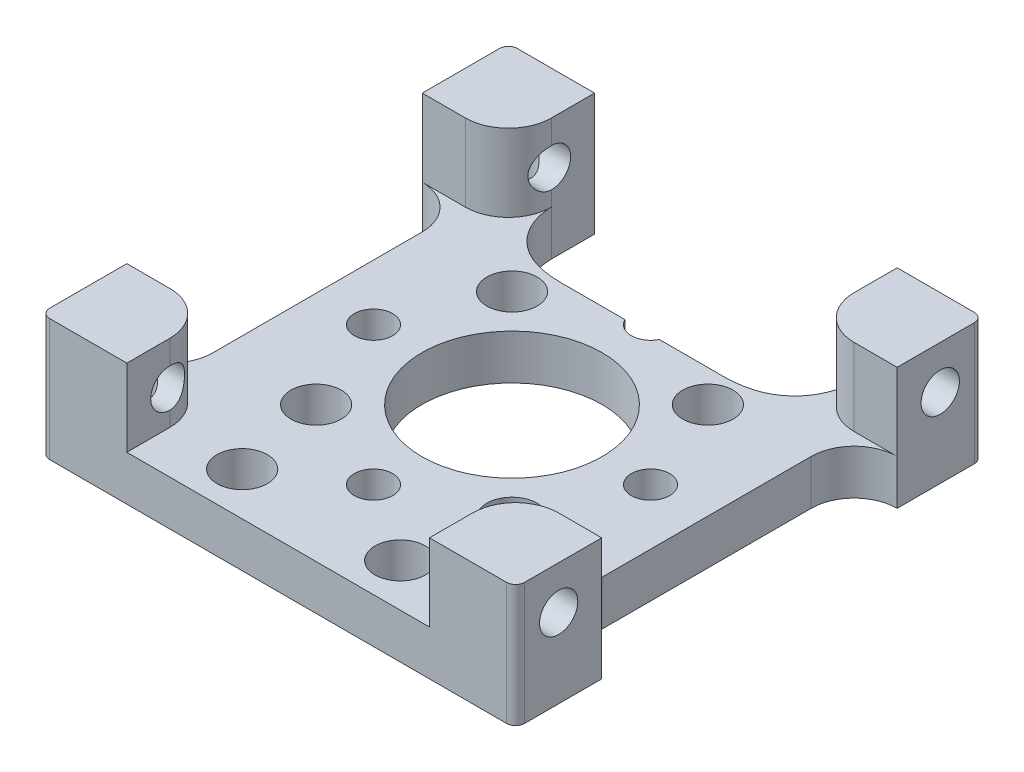
SolidWorks part; units mm, degrees
ref_plane "Front Plane" through (0, 0, 0) normal (0, 0, 1) x (1, 0, 0)
ref_plane "Top Plane" through (0, 0, 0) normal (0, 1, 0) x (1, 0, 0)
ref_plane "Right Plane" through (0, 0, 0) normal (1, 0, 0) x (0, 0, -1)
ref_plane "Plane1" through (0, 3.175, 0) normal (0, 1, 0) x (1, 0, 0)
sketch "Sketch1" plane through (0, 3.175, 0) normal (0, 1, 0) x (1, 0, 0)
  line L0 (16.764, -16.51) -> (16.764, 16.51)
  line L1 (16.764, 16.51) -> (-16.764, 16.51)
  line L2 (-16.764, 16.51) -> (-16.764, -16.51)
  line L3 (-16.764, -16.51) -> (16.764, -16.51)
extrude "Boss-Extrude1" add sketch "Sketch1" against normal blind 3.175
sketch "Sketch2" plane through (0, 0, 0) normal (0, -1, 0) x (1, 0, 0)
  line L0 (16.764, -10.4292) -> (16.764, 10.4292)
  line L1 (13.7287, 7.3889) -> (13.7287, -7.3889)
  arc A0 (16.764, 10.4292) -> (13.7287, 7.3889) centre (16.7691, 7.3889) ccw
  arc A1 (13.7287, -7.3889) -> (16.764, -10.4292) centre (16.7691, -7.3889) ccw
extrude "Cut-Extrude1" cut sketch "Sketch2" against normal through all
sketch "Sketch3" plane through (0, 0, 0) normal (0, -1, 0) x (1, 0, 0)
  line L0 (-16.764, 10.4292) -> (-16.764, -10.4292)
  line L1 (-13.7287, -7.3889) -> (-13.7287, 7.3889)
  arc A0 (-16.764, -10.4292) -> (-13.7287, -7.3889) centre (-16.7691, -7.3889) ccw
  arc A1 (-13.7287, 7.3889) -> (-16.764, 10.4292) centre (-16.7691, 7.3889) ccw
extrude "Cut-Extrude2" cut sketch "Sketch3" against normal through all
ref_plane "Plane2" through (0, 0, -16.51) normal (0, 0, -1) x (-1, 0, 0)
sketch "Sketch4" plane through (0, 0, -16.51) normal (0, 0, -1) x (-1, 0, 0)
  line L0 (10.6832, 3.175) -> (16.764, 3.175)
  line L1 (16.764, 3.175) -> (16.764, 8.6284)
  line L2 (16.764, 8.6284) -> (10.6832, 8.6284)
  line L3 (10.6832, 8.6284) -> (10.6832, 3.175)
extrude "Boss-Extrude2" add sketch "Sketch4" against normal blind 6.0808
sketch "Sketch5" plane through (0, 0, -16.51) normal (0, 0, -1) x (-1, 0, 0)
  line L0 (-16.764, 8.6284) -> (-16.764, 3.175)
  line L1 (-16.764, 3.175) -> (-10.6832, 3.175)
  line L2 (-10.6832, 3.175) -> (-10.6832, 8.6284)
  line L3 (-10.6832, 8.6284) -> (-16.764, 8.6284)
extrude "Boss-Extrude3" add sketch "Sketch5" against normal blind 6.0808
ref_plane "Plane3" through (0, 0, 16.51) normal (0, 0, 1) x (1, 0, 0)
sketch "Sketch6" plane through (0, 0, 16.51) normal (0, 0, 1) x (1, 0, 0)
  line L0 (10.6832, 3.175) -> (16.764, 3.175)
  line L1 (16.764, 3.175) -> (16.764, 8.6284)
  line L2 (16.764, 8.6284) -> (10.6832, 8.6284)
  line L3 (10.6832, 8.6284) -> (10.6832, 3.175)
extrude "Boss-Extrude4" add sketch "Sketch6" against normal blind 6.0808
sketch "Sketch7" plane through (0, 0, 16.51) normal (0, 0, 1) x (1, 0, 0)
  line L0 (-16.764, 8.6284) -> (-16.764, 3.175)
  line L1 (-16.764, 3.175) -> (-10.6832, 3.175)
  line L2 (-10.6832, 3.175) -> (-10.6832, 8.6284)
  line L3 (-10.6832, 8.6284) -> (-16.764, 8.6284)
extrude "Boss-Extrude5" add sketch "Sketch7" against normal blind 6.0808
hole_wizard "Hole1" positions "Sketch9" profile "Sketch8" legacy
sketch "Sketch9" plane through (0, 3.175, 0) normal (0, 1, 0) x (1, 0, 0)
  point P0 (0, 0)
sketch "Sketch8" plane through (0, 3.175, 0) normal (1, 0, 0) x (0, 0, 1)
  line L0 (0, 0) -> (0, 3.175)
  line L1 (0, 3.175) -> (6.3627, 3.175)
  line L2 (6.3627, 3.175) -> (6.3627, 0)
  line L3 (6.3627, 0) -> (0, 0)
  line L4 (0, 110) -> (0, -10) construction
  dimension "Diameter" = 12.7254
  dimension "Depth" = 3.175
hole_wizard "M2.5 Clearance Hole1" positions "Sketch11" profile "Sketch10" hole size "M2.5" standard "ANSI Metric"
sketch "Sketch11" plane through (0, 3.175, 0) normal (0, 1, 0) x (1, 0, 0)
  point P0 (0, 9.779)
  point P1 (-9.779, 0)
  point P2 (0, -9.779)
  point P3 (9.779, 0)
sketch "Sketch10" plane through (0, 3.175, -9.779) normal (1, 0, 0) x (0, 0, 1)
  line L0 (0, 0) -> (0, 3.175)
  line L1 (0, 3.175) -> (1.3525, 3.175)
  line L2 (1.3525, 3.175) -> (1.3525, 0)
  line L5 (1.3525, 0) -> (0, 0)
  line L11 (0, -6.35) -> (0, 107.95) construction
  dimension "Thru Hole Dia." = 2.7051
  dimension "Thru Hole Depth" = 3.175
hole_wizard "M3 Clearance Hole1" positions "Sketch13" profile "Sketch12" hole size "M3" standard "ANSI Metric"
sketch "Sketch13" plane through (0, 3.175, 0) normal (0, 1, 0) x (1, 0, 0)
  point P0 (-5.5796, -13.4704)
  point P1 (5.5796, -13.4704)
  point P2 (5.5796, 13.4704)
  point P3 (-5.5796, 13.4704)
  point P4 (6.9148, 6.9148)
  point P5 (-6.9148, 6.9148)
  point P6 (-6.9148, -6.9148)
  point P7 (6.9148, -6.9148)
sketch "Sketch12" plane through (-5.5796, 3.175, 13.4704) normal (1, 0, 0) x (0, 0, 1)
  line L0 (0, 0) -> (0, 3.175)
  line L1 (0, 3.175) -> (1.778, 3.175)
  line L2 (1.778, 3.175) -> (1.778, 0)
  line L5 (1.778, 0) -> (0, 0)
  line L11 (0, -6.35) -> (0, 107.95) construction
  dimension "Thru Hole Dia." = 3.556
  dimension "Thru Hole Depth" = 3.175
hole_wizard "M2.5 Clearance Hole2" positions "Sketch15" profile "Sketch14" hole size "M2.5" standard "ANSI Metric"
sketch "Sketch15" plane through (16.764, 0, 0) normal (1, 0, 0) x (0, 0, -1)
  point P0 (-13.4704, 5.588)
sketch "Sketch14" plane through (16.764, 5.588, 13.4704) normal (0, 1, 0) x (0, 0, -1)
  line L0 (0, 0) -> (0, 39.6088)
  line L1 (0, 39.6088) -> (1.3525, 39.6088)
  line L2 (1.3525, 39.6088) -> (1.3525, 0)
  line L5 (1.3525, 0) -> (0, 0)
  line L10 (0, 39.6088) -> (-1.3525, 39.6088) construction
  line L11 (0, -6.35) -> (0, 107.95) construction
  dimension "Hole Dia." = 2.7051
  dimension "Hole Depth" = 39.6088
  dimension "Drill Angle" = 180
hole_wizard "M2.5 Clearance Hole3" positions "Sketch17" profile "Sketch16" hole size "M2.5" standard "ANSI Metric"
sketch "Sketch17" plane through (-16.764, 0, 0) normal (-1, 0, 0) x (0, 0, 1)
  point P0 (-13.4704, 5.588)
sketch "Sketch16" plane through (-16.764, 5.588, -13.4704) normal (0, 1, 0) x (0, 0, 1)
  line L0 (0, 0) -> (0, 39.6088)
  line L1 (0, 39.6088) -> (1.3525, 39.6088)
  line L2 (1.3525, 39.6088) -> (1.3525, 0)
  line L5 (1.3525, 0) -> (0, 0)
  line L10 (0, 39.6088) -> (-1.3525, 39.6088) construction
  line L11 (0, -6.35) -> (0, 107.95) construction
  dimension "Hole Dia." = 2.7051
  dimension "Hole Depth" = 39.6088
  dimension "Drill Angle" = 180
hole_wizard "M2.5 Clearance Hole4" positions "Sketch19" profile "Sketch18" hole size "M2.5" standard "ANSI Metric"
sketch "Sketch19" plane through (0, 0, 0) normal (0, -1, 0) x (-1, 0, 0)
  point P0 (13.4704, 13.4704)
  point P1 (-13.4704, 13.4704)
  point P2 (-13.4704, -13.4704)
  point P3 (13.4704, -13.4704)
sketch "Sketch18" plane through (-13.4704, 0, -13.4704) normal (1, 0, 0) x (0, 0, -1)
  line L0 (0, 0) -> (0, 4.2355)
  line L1 (0, 4.2355) -> (1.3525, 4.2355)
  line L2 (1.3525, 4.2355) -> (1.3525, 0)
  line L5 (1.3525, 0) -> (0, 0)
  line L11 (0, -6.35) -> (0, 107.95) construction
  dimension "Thru Hole Dia." = 2.7051
  dimension "Thru Hole Depth" = 4.2355
fillet "Fillet1" radius 0.635 4 edges at (-16.764, 4.3142, -16.51) (-16.764, 4.3142, 16.51) (16.764, 4.3142, 16.51) (16.764, 4.3142, -16.51) tangent propagation no
fillet "Fillet2" radius 3.0404 4 edges at (-10.6832, 5.9017, -10.4292) (10.6832, 5.9017, -10.4292) (10.6832, 5.9017, 10.4292) (-10.6832, 5.9017, 10.4292) tangent propagation no
sketch "Sketch20" plane through (0, 3.175, 0) normal (0, 1, 0) x (1, 0, 0)
  line L0 (10.6832, 13.4696) -> (10.6832, 16.51) construction
  line L1 (5.8151, 9.1861) -> (-5.8151, 9.1861)
  line L2 (0, 8.4265) -> (0, 17.3326) construction
  line L3 (10.6832, 13.4696) -> (10.6832, 16.51)
  line L4 (10.6832, 16.51) -> (-10.6832, 16.51)
  line L5 (-10.6832, 16.51) -> (-10.6832, 13.4696)
  arc A0 (10.6832, 13.4696) -> (7.6744, 9.4528) centre (6.4976, 13.4696) cw
  arc A1 (7.6744, 9.4528) -> (5.8151, 9.1861) centre (5.8151, 15.799) cw
  circle A2 centre (0, 9.779) radius 1.3525 construction
  arc A3 (-10.6832, 13.4696) -> (-7.6744, 9.4528) centre (-6.4976, 13.4696) ccw
  arc A4 (-7.6744, 9.4528) -> (-5.8151, 9.1861) centre (-5.8151, 15.799) ccw
  point P20 (0, 9.1861)
extrude "Cut-Extrude3" cut sketch "Sketch20" against normal up to next
